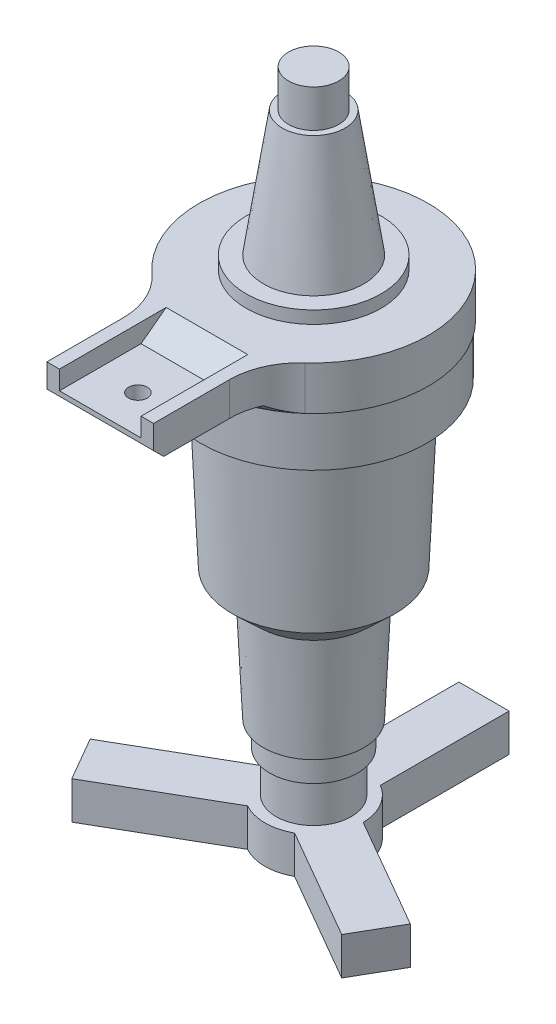
SolidWorks part; units mm, degrees
ref_plane "Face" through (0, 0, 0) normal (0, 0, 1) x (1, 0, 0)
ref_plane "Dessus" through (0, 0, 0) normal (0, 1, 0) x (1, 0, 0)
ref_plane "Droite" through (0, 0, 0) normal (1, 0, 0) x (0, 0, -1)
sketch "Esquisse1" plane through (0, 0, 0) normal (0, 1, 0) x (1, 0, 0)
  circle A0 centre (0, 0) radius 12.3031
  dimension "D1" = 24.6062
extrude "Boss.-Extru.1" add sketch "Esquisse1" along normal blind 9.525
sketch "Esquisse2" plane through (0, 9.525, 0) normal (0, 1, 0) x (1, 0, 0)
  line L1 (-6.35, 10.5378) -> (6.35, 10.5378)
  line L2 (-6.35, 10.5378) -> (-6.35, 43.0815)
  line L3 (-6.35, 43.0815) -> (6.35, 43.0815)
  line L4 (6.35, 10.5378) -> (6.35, 43.0815)
  circle A0 centre (0, 0) radius 12.3031 construction
  dimension "D1" = 32.5437
  dimension "D2" = 12.7
extrude "Boss.-Extru.2" add sketch "Esquisse2" against normal blind 9.525
pattern_circular "Répétition circulaire1" count 3 over 360 about axis through (0, 9.525, 0) along (0, 1, 0) of "Boss.-Extru.2"
sketch "Esquisse3" plane through (0, 9.525, 0) normal (0, 1, 0) x (1, 0, 0)
  circle A0 centre (0, 0) radius 9.525
  dimension "D1" = 19.05
extrude "Boss.-Extru.3" add sketch "Esquisse3" along normal blind 10.3187
sketch "Esquisse4" plane through (0, 19.8438, 0) normal (0, 1, 0) x (1, 0, 0)
  circle A0 centre (0, 0) radius 11.1125
  dimension "D1" = 22.225
extrude "Boss.-Extru.4" add sketch "Esquisse4" along normal blind 6.35
sketch "Esquisse5" plane through (0, 0, 0) normal (0, 0, 1) x (1, 0, 0)
  line L0 (0, 26.1938) -> (0, 53.1812)
  line L1 (11.1125, 26.1938) -> (-11.1125, 26.1938) construction
  line L3 (13.8906, 53.1812) -> (12.7, 26.1938)
  line L4 (12.7, 26.1938) -> (0, 26.1938)
  line L5 (13.8906, 53.1812) -> (20.6375, 59.5312)
  line L6 (20.6375, 59.5312) -> (22.225, 97.6313)
  line L7 (22.225, 97.6313) -> (23.8125, 100.8063)
  line L8 (23.8125, 100.8063) -> (28.575, 100.8063)
  line L9 (28.575, 100.8063) -> (28.575, 113.5063)
  line L10 (28.575, 113.5063) -> (0, 113.5063)
  line L11 (0, 113.5063) -> (0, 53.1812)
  dimension "D1" = 26.9875
  dimension "D2" = 13.8906
  dimension "D3" = 12.7
  dimension "D4" = 6.35
  dimension "D5" = 20.6375
  dimension "D6" = 38.1
  dimension "D7" = 3.175
  dimension "D8" = 1.5875
  dimension "D9" = 6.35
  dimension "D10" = 12.7
  dimension "D11" = 28.575
  dimension "D12" = 135.65
revolve "Révolution1" add sketch "Esquisse5" angle 360 about L0
sketch "Esquisse6" plane through (0, 113.5063, 0) normal (0, 1, 0) x (1, 0, 0)
  circle A0 centre (0, 0) radius 28.9719
  dimension "D1" = 57.9437
extrude "Boss.-Extru.5" add sketch "Esquisse6" along normal blind 11.1125
sketch "Esquisse7" plane through (0, 124.6188, 0) normal (0, 1, 0) x (1, 0, 0)
  line L1 (-13.4938, -25.6376) -> (13.4938, -25.6376)
  line L2 (-13.4938, -25.6376) -> (-13.4937, -53.975)
  line L3 (-13.4937, -53.975) -> (13.4937, -53.975)
  line L4 (13.4938, -25.6376) -> (13.4937, -53.975)
  circle A0 centre (0, 0) radius 28.9719 construction
  dimension "D1" = 26.9875
  dimension "D2" = 53.975
extrude "Boss.-Extru.6" add sketch "Esquisse7" against normal blind 8.509
fillet "Congé1" radius 17.78 2 edges at (-13.4938, 120.3643, 25.6376) (13.4938, 120.3643, 25.6376)
sketch "Esquisse8" plane through (0, 124.6188, 0) normal (0, 1, 0) x (1, 0, 0)
  line L0 (-13.4937, -53.975) -> (13.4937, -53.975) construction
  line L1 (-13.4938, -34.7518) -> (-13.4937, -53.975) construction
  line L2 (-10.3188, -53.975) -> (10.3187, -53.975)
  line L3 (-10.3188, -53.975) -> (-10.3188, -26.9875)
  line L4 (-10.3188, -26.9875) -> (10.3187, -26.9875)
  line L5 (10.3187, -53.975) -> (10.3187, -26.9875)
  line L6 (13.4937, -53.975) -> (13.4938, -34.7518) construction
  dimension "D1" = 3.175
  dimension "D2" = 3.175
  dimension "D3" = 26.9875
extrude "Enlèv. mat.-Extru.1" cut sketch "Esquisse8" against normal blind 4.7625
chamfer "Chanfrein2" distance 2.54 angle 45 2 edges at (0, 116.1097, 28.9719) (0, 116.1097, 53.975)
chamfer "Chanfrein3" distance 4.7625 distance2 6.35 1 edges at (0, 119.8563, 26.9875) first distance on face at (0, 122.2375, 26.9875)
sketch "Esquisse9" plane through (0, 119.8563, 0) normal (0, 1, 0) x (1, 0, 0)
  line L0 (-10.3188, -53.975) -> (10.3187, -53.975) construction
  circle A0 centre (0, -44.45) radius 2.3812
  dimension "D1" = 4.7625
  dimension "D2" = 9.525
extrude "Enlèv. mat.-Extru.2" cut sketch "Esquisse9" against normal up to next
sketch "Esquisse11" plane through (0, 0, 0) normal (0, 0, 1) x (1, 0, 0)
  line L0 (0, 124.6188) -> (17.0656, 124.6188)
  line L1 (10.3187, 124.6188) -> (-10.3188, 124.6188) construction
  line L2 (28.9719, 124.6188) -> (-28.9719, 124.6188) construction
  line L3 (17.0656, 124.6188) -> (17.0656, 127.7938)
  line L4 (17.0656, 127.7938) -> (12.7, 127.7938)
  line L5 (12.7, 127.7938) -> (7.9375, 159.5438)
  line L6 (7.9375, 159.5438) -> (6.35, 159.5438)
  line L7 (6.35, 159.5438) -> (6.35, 169.0688)
  line L8 (6.35, 169.0688) -> (0, 169.0688)
  line L9 (0, 169.0688) -> (0, 124.6188)
  dimension "D1" = 3.175
  dimension "D2" = 17.0656
  dimension "D3" = 12.7
  dimension "D4" = 7.9375
  dimension "D5" = 1.5875
  dimension "D6" = 31.75
  dimension "D7" = 9.525
revolve "Révolution2" add sketch "Esquisse11" angle 360 about L9
